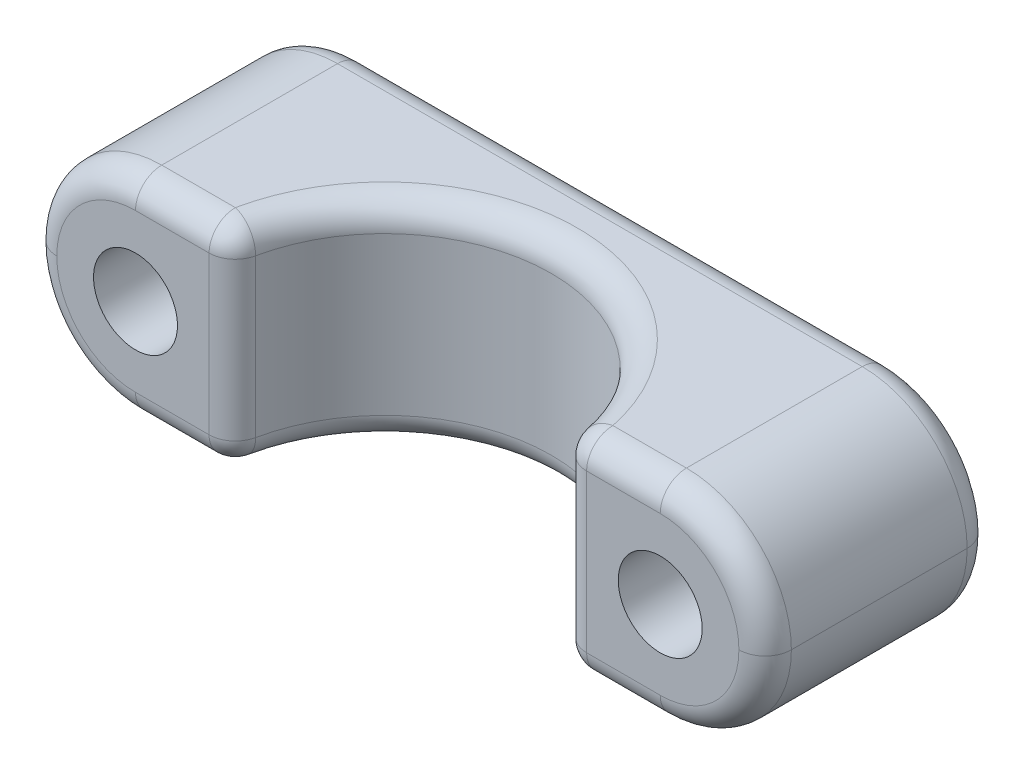
SolidWorks part; units mm, degrees
ref_plane "Спереди" through (0, 0, 0) normal (0, 0, 1) x (1, 0, 0)
ref_plane "Сверху" through (0, 0, 0) normal (0, 1, 0) x (1, 0, 0)
ref_plane "Справа" through (0, 0, 0) normal (1, 0, 0) x (0, 0, -1)
sketch "Эскиз1" plane through (0, 0, 0) normal (0, 1, 0) x (1, 0, 0)
  line L0 (0, 7.3902) -> (0, -4.7625) construction
  line L1 (-5.3866, 0) -> (8.9339, 0) construction
  line L2 (-31.1372, 16) -> (34.4217, 16) construction
  line L3 (14, 9.2) -> (-14, 9.2)
  line L4 (-6.45, 15) -> (6.45, 15) construction
  line L5 (-6.45, 15) -> (-6.45, 9.2) construction
  line L6 (-6.45, 9.2) -> (6.45, 9.2) construction
  line L7 (6.45, 15) -> (6.45, 9.2) construction
  line L8 (-6.45, 15) -> (6.45, 9.2) construction
  line L9 (-6.45, 9.2) -> (6.45, 15) construction
  line L10 (-14, 9.2) -> (-14, 0.5)
  line L11 (-6.3303, 0.5) -> (-14, 0.5)
  line L12 (6.3303, 0.5) -> (14, 0.5)
  line L13 (14, 0.5) -> (14, 9.2)
  arc A0 (6.3303, 0.5) -> (-6.3303, 0.5) centre (0, 0) ccw
  point P8 (0, 12.1)
  point P17 (0, 9.2)
  dimension "D1" = 12.7
  dimension "D2" = 16
  dimension "D3" = 5.8
  dimension "D4" = 12.9
  dimension "D5" = 1
  dimension "D6" = 1
  dimension "D7" = 14
extrude "Бобышка-Вытянуть1" add sketch "Эскиз1" along normal blind 8
fillet "Скругление1" radius 4 4 edges at (14, 0, -4.85) (14, 8, -4.85) (-14, 0, -4.85) (-14, 8, -4.85)
sketch "Эскиз3" plane through (0, 0, -9.2) normal (0, 0, 1) x (1, 0, 0)
  line L0 (0, 11.7982) -> (0, -5.5686) construction
  line L1 (3.25, 4) -> (-3.25, 4) construction
  circle A0 centre (-3.25, 4) radius 0.75
  circle A1 centre (3.25, 4) radius 0.75
  point P7 (0, 4)
  dimension "D3" = 1.5
  dimension "D1" = 4
  dimension "D2" = 6.5
extrude "Вырез-Вытянуть1" cut sketch "Эскиз3" along normal blind 3
sketch "Эскиз4" plane through (0, 0, -0.5) normal (0, 0, 1) x (1, 0, 0)
  circle A0 centre (-10, 4) radius 1.6
  circle A1 centre (10, 4) radius 1.6
  dimension "D1" = 3.2
extrude "Вырез-Вытянуть2" cut sketch "Эскиз4" against normal through all
sketch "Эскиз5" plane through (0, 0, -9.2) normal (0, 0, -1) x (-1, 0, 0)
  circle A0 centre (-10, 4) radius 3
  circle A1 centre (10, 4) radius 3
  dimension "D1" = 6
extrude "Вырез-Вытянуть3" cut sketch "Эскиз5" against normal blind 2
fillet "Скругление3" radius 1 8 edges at (12.8284, 6.8284, -9.2) (12.8284, 1.1716, -9.2) (0, 0, -9.2) (-12.8284, 1.1716, -9.2) (-12.8284, 6.8284, -9.2) (0, 8, -9.2) (-13, 4, -9.2) (7, 4, -9.2)
fillet "Скругление2" radius 1 12 edges at (8.1651, 0, -0.5) (12.8284, 1.1716, -0.5) (12.8284, 6.8284, -0.5) (-8.1651, 8, -0.5) (-12.8284, 6.8284, -0.5) (-12.8284, 1.1716, -0.5) (8.1651, 8, -0.5) (0, 8, -6.35) (0, 0, -6.35) (-8.1651, 0, -0.5) (-6.3303, 4, -0.5) (6.3303, 4, -0.5)
sketch "Эскиз6" plane through (0, 0, -9.2) normal (0, 0, -1) x (-1, 0, 0)
  line L0 (10, 0) -> (-10, 0) construction
  line L1 (-6.45, 1) -> (6.45, 1)
  line L2 (-6.45, 1) -> (-6.45, 0)
  line L3 (-6.45, 0) -> (6.45, 0)
  line L4 (6.45, 1) -> (6.45, 0)
  line L5 (-6.45, 1) -> (6.45, 0) construction
  line L6 (-6.45, 0) -> (6.45, 1) construction
  point P0 (0, 0.5)
  dimension "D1" = 12.9
  dimension "D2" = 1
extrude "Бобышка-Вытянуть2" add sketch "Эскиз6" against normal blind 1
